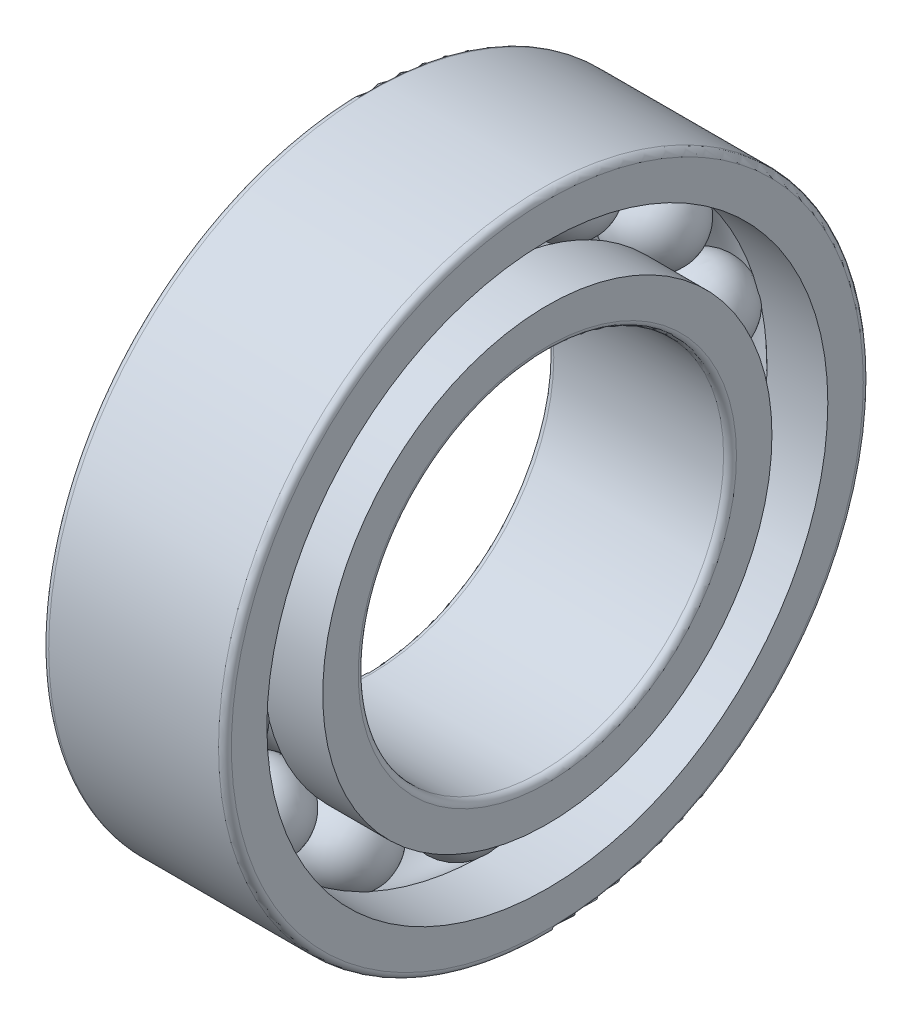
SolidWorks part; units mm, degrees
ref_plane "Plane1" through (0, 0, 0) normal (0, 0, 1) x (1, 0, 0)
ref_plane "Plane2" through (0, 0, 0) normal (0, 1, 0) x (1, 0, 0)
ref_plane "Plane3" through (0, 0, 0) normal (1, 0, 0) x (0, 0, -1)
sketch "Clipboard" plane through (0, 0, 0) normal (0, 0, 1) x (1, 0, 0)
  line L0 (-10, 0) -> (10, 0) construction
  line L1 (0, 0) -> (21.6965, -5.4095)
  line L2 (0, 0) -> (11.401, 2.8426)
  line L3 (0, 0) -> (21.6965, -5.4095)
  line L4 (0, 0) -> (-22.3573, -0.3902)
  dimension "BallCLRad" = 11.75
  dimension "Count" = 14
  dimension "Show_count" = 14
  dimension "Max_count" = 14
  dimension "Min_count" = 1
sketch "CagSpiSke" plane through (0, 0, 0) normal (0, 0, 1) x (1, 0, 0)
  line L0 (0.195, 11.425) -> (0.195, 12.075)
  line L1 (0.195, 12.075) -> (-0.195, 12.075)
  line L2 (-0.195, 12.075) -> (-0.195, 11.425)
  line L3 (-0.195, 11.425) -> (0.195, 11.425)
  line L4 (-20.6375, 0) -> (20.6375, 0) construction
  line L5 (0, 0) -> (0, 23.7692) construction
  dimension "Thickness" = 0.39
  dimension "OD" = 24.15
  dimension "ID" = 22.85
revolve "CageSpine" add sketch "CagSpiSke" angle 0.001 about L4 reverse direction yes
ref_axis "Axis1" through (-50, 0, 0) along (1, 0, 0)
sketch "CagBalSke" plane through (0, 0, 0) normal (0, 0, 1) x (1, 0, 0)
  line L0 (-2.145, 11.75) -> (2.145, 11.75)
  line L1 (-1.905, 11.75) -> (1.905, 11.75) construction
  line L2 (-10, 0) -> (10, 0) construction
  line L3 (0, 0) -> (0, 24) construction
  arc A0 (2.145, 11.75) -> (-2.145, 11.75) centre (0, 11.75) cw
  dimension "CageWallOD" = 4.29
  dimension "BallCLRad" = 11.75
revolve "CageBall" [suppressed] add sketch "CagBalSke" angle 360 about L1 reverse direction yes
pattern_circular "CageBalls" [suppressed] count 14 every 25.714 about axis through (-50, 0, 0) along (1, 0, 0)
sketch "CagTrmODSke" plane through (0, 0, 0) normal (0, 0, 1) x (1, 0, 0)
  line L0 (2.146, 12.075) -> (2.146, 13.896)
  line L1 (2.146, 13.896) -> (-2.146, 13.896)
  line L2 (-2.146, 13.896) -> (-2.146, 12.075)
  line L3 (-2.146, 12.075) -> (2.146, 12.075)
  line L4 (-20.6375, 0) -> (20.6375, 0) construction
  line L5 (0, 0) -> (0, 25) construction
  dimension "Width" = 4.292
  dimension "ID" = 24.15
  dimension "OD" = 27.792
revolve "CageTrimOD" [suppressed] cut sketch "CagTrmODSke" angle 360 about L4 reverse direction yes
sketch "CagTrmIDSke" plane through (0, 0, 0) normal (0, 0, 1) x (1, 0, 0)
  line L0 (2.146, 9.606) -> (2.146, 11.425)
  line L1 (2.146, 11.425) -> (-2.146, 11.425)
  line L2 (-2.146, 11.425) -> (-2.146, 9.606)
  line L3 (-2.146, 9.606) -> (2.146, 9.606)
  line L4 (-20.6375, 0) -> (20.6375, 0) construction
  line L5 (0, 0) -> (0, 25) construction
  dimension "ID" = 19.212
  dimension "OD" = 22.85
  dimension "Width" = 4.292
revolve "CageTrimID" [suppressed] cut sketch "CagTrmIDSke" angle 360 about L4 reverse direction yes
sketch "BalSimSke" plane through (0, 0, 0) normal (0, 0, 1) x (1, 0, 0)
  line L0 (-10, 0) -> (10, 0) construction
  line L1 (-10, 11.75) -> (10, 11.75) construction
  line L2 (0, 0) -> (0, 23) construction
  circle A0 centre (0, 11.75) radius 1.95
  dimension "Ball_diameter" = 3.9
  dimension "BallCLRad" = 11.75
revolve "BallsSimplified" [suppressed] add sketch "BalSimSke" angle 360 about L0
sketch "BalDetSke" plane through (0, 0, 0) normal (0, 0, 1) x (1, 0, 0)
  line L0 (-1.95, 11.75) -> (1.95, 11.75)
  line L1 (-1.905, 11.75) -> (1.905, 11.75) construction
  line L2 (0, 0) -> (0, 25) construction
  arc A0 (1.95, 11.75) -> (-1.95, 11.75) centre (0, 11.75) cw
  dimension "Ball_diameter" = 3.9
  dimension "BallCLRad" = 11.75
revolve "BallDetailed" add sketch "BalDetSke" angle 360 about L1 reverse direction yes
sketch "InnRacSke" plane through (0, 0, 0) normal (0, 0, 1) x (1, 0, 0)
  line L0 (-1.4197, 10.45) -> (-4.25, 10.45)
  line L1 (-4.25, 10.45) -> (-4.25, 8.8)
  line L2 (-3.95, 8.5) -> (3.95, 8.5)
  line L3 (4.25, 8.8) -> (4.25, 10.45)
  line L4 (4.25, 10.45) -> (1.4197, 10.45)
  line L5 (-20.6375, 0) -> (20.6375, 0) construction
  line L6 (0, 0) -> (0, 30) construction
  arc A0 (-4.25, 8.8) -> (-3.95, 8.5) centre (-3.95, 8.8) ccw
  arc A1 (3.95, 8.5) -> (4.25, 8.8) centre (3.95, 8.8) ccw
  arc A2 (1.4197, 10.45) -> (-1.4197, 10.45) centre (0, 11.75) cw
  dimension "Fillet_radius" = 0.3
  dimension "Ball_diameter" = 3.85
  dimension "ID" = 17
  dimension "OD" = 20.9
  dimension "Width" = 8.5
  dimension "BallCLRad" = 11.75
revolve "InnerRace" add sketch "InnRacSke" angle 360 about L5 reverse direction yes
sketch "OutRacSke" plane through (0, 0, 0) normal (0, 0, 1) x (1, 0, 0)
  line L0 (-1.4197, 13.05) -> (-4.25, 13.05)
  line L1 (-4.25, 13.05) -> (-4.25, 14.7)
  line L2 (-3.95, 15) -> (3.95, 15)
  line L3 (4.25, 14.7) -> (4.25, 13.05)
  line L4 (4.25, 13.05) -> (1.4197, 13.05)
  line L5 (-20.6375, 0) -> (20.6375, 0) construction
  line L6 (0, 0) -> (0, 30) construction
  arc A0 (-4.25, 14.7) -> (-3.95, 15) centre (-3.95, 14.7) cw
  arc A1 (3.95, 15) -> (4.25, 14.7) centre (3.95, 14.7) cw
  arc A2 (1.4197, 13.05) -> (-1.4197, 13.05) centre (0, 11.75) ccw
  dimension "Fillet_radius" = 0.3
  dimension "Ball_diameter" = 3.85
  dimension "OD" = 30
  dimension "ID" = 26.1
  dimension "Width" = 8.5
  dimension "BallCLRad" = 11.75
revolve "OuterRace" add sketch "OutRacSke" angle 360 about L5 reverse direction yes
pattern_circular "BallsDetailed" count 14 every 25.714 about axis through (-50, 0, 0) along (1, 0, 0) of "BallDetailed"
equation "\"BallCLRad@Clipboard\" = ( \"OD@OutRacSke\" + \"ID@InnRacSke\" ) / 4"
equation "\"BallCLRad@BalSimSke\" = \"BallCLRad@Clipboard\""
equation "\"BallCLRad@BalDetSke\" = \"BallCLRad@Clipboard\""
equation "\"BallCLRad@InnRacSke\" = \"BallCLRad@Clipboard\""
equation "\"BallCLRad@OutRacSke\" = \"BallCLRad@Clipboard\""
equation "\"Ball_diameter@InnRacSke\" = \"Ball_diameter@BalDetSke\" - 0.05"
equation "\"Ball_diameter@OutRacSke\" = \"Ball_diameter@BalDetSke\" - 0.05"
equation "\"Ball_diameter@BalSimSke\" = \"Ball_diameter@BalDetSke\""
equation "\"Width@OutRacSke\" = \"Width@InnRacSke\""
equation "\"Fillet_radius@OutRacSke\" = \"Fillet_radius@InnRacSke\""
equation "\"Max_count@Clipboard\" = int( 3.14159265 / atn(( \"Ball_diameter@BalDetSke\" / 2) / sqr( \"BallCLRad@Clipboard\"  *  \"BallCLRad@Clipboard\" - ( \"Ball_diameter@BalDetSke\" / 2) *  ( \"Ball_diameter@BalDetSke\" / 2))))"
equation "\"Max_count@Clipboard\" = ((sgn( \"Max_count@Clipboard\" - \"Count@Clipboard\" )-1)*( \"Max_count@Clipboard\" - \"Count@Clipboard\" ))/-2+ \"Count@Clipboard\""
equation "\"Count@BallsDetailed\" = int( \"Show_count@Clipboard\" ) "
equation "\"Count@BallsDetailed\" = ((sgn( \"Count@BallsDetailed\" - \"Max_count@Clipboard\" )-1)*( \"Count@BallsDetailed\" - \"Max_count@Clipboard\" ))/-2+ \"Max_count@Clipboard\""
equation "\"Count@BallsDetailed\" = ((sgn( \"Count@BallsDetailed\" - \"Min_count@Clipboard\" )+1)*( \"Count@BallsDetailed\" - \"Min_count@Clipboard\"))/2 +\"Min_count@Clipboard\""
equation "\"Angle@BallsDetailed\" = 360.0 / \"Max_count@Clipboard\""
equation "\"BallCLRad@CagBalSke\" = \"BallCLRad@Clipboard\""
equation "\"Count@CageBalls\" = \"Count@BallsDetailed\""
equation "\"Angle@CageBalls\" = \"Angle@BallsDetailed\""
equation "\"Angle@CageSpine\" =  \"Angle@CageBalls\" * ( \"Count@CageBalls\" -1 + int( \"Count@CageBalls\" / \"Max_count@Clipboard\" ) )  + 0.001 -  int( \"Count@CageBalls\" / \"Max_count@Clipboard\" ) * 0.001"
equation "\"Angle@CageSpine\" =  \"Angle@CageSpine\" * int( \"Min_count@Clipboard\" / 2) + int(1 / \"Min_count@Clipboard\")  * 0.001"
equation "\"CageWallOD@CagBalSke\" =  \"Ball_diameter@BalDetSke\" * 1.1"
equation "\"Thickness@CagSpiSke\" =  \"Ball_diameter@BalDetSke\" * 0.1"
equation "\"OD@CagTrmODSke\" = \"BallCLRad@Clipboard\" * 2 + \"CageWallOD@CagBalSke\" + 0.002"
equation "\"ID@CagTrmODSke\" = \"BallCLRad@Clipboard\" * 2 + \"Ball_diameter@BalDetSke\" / 6"
equation "\"OD@CagTrmIDSke\" = \"BallCLRad@Clipboard\" * 2 - \"Ball_diameter@BalDetSke\" / 6"
equation "\"ID@CagTrmIDSke\" = \"BallCLRad@Clipboard\" * 2 - \"CageWallOD@CagBalSke\" + 0.002"
equation "\"OD@CagSpiSke\" = \"ID@CagTrmODSke\""
equation "\"ID@CagSpiSke\" = \"OD@CagTrmIDSke\""
equation "\"Width@CagTrmODSke\" = \"CageWallOD@CagBalSke\" + 0.002"
equation "\"Width@CagTrmIDSke\" = \"CageWallOD@CagBalSke\" + 0.002"
